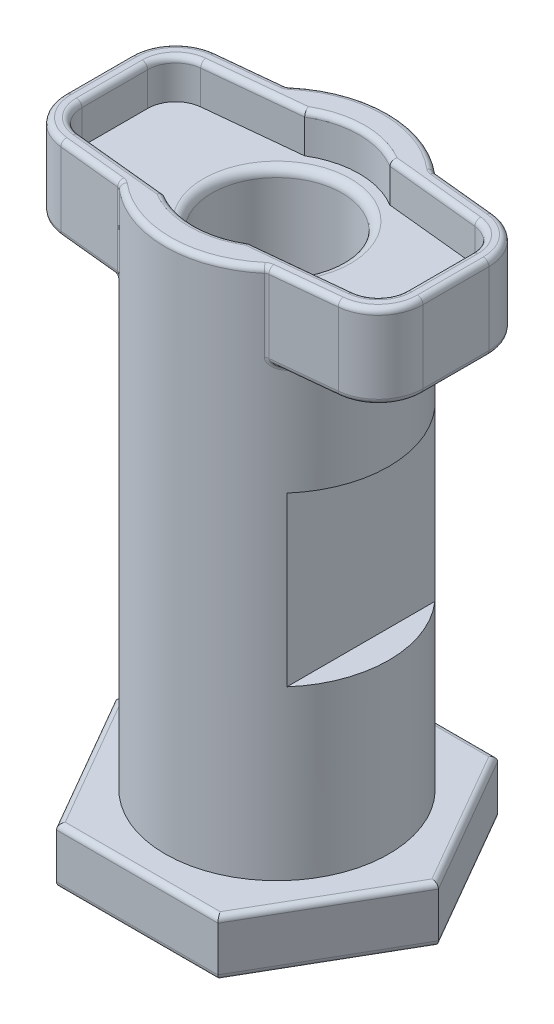
SolidWorks part; units mm, degrees
other "Markup1"
sketch "Sketch1" plane through (0, 0, 0) normal (0.5774, 0.5773, 0.5774) x (0.7071, 0, -0.7071)
sketch "Sketch2" plane through (0, 0, 0) normal (0.5774, 0.5773, 0.5774) x (0.7071, 0, -0.7071)
ref_plane "Front (z)" through (0, 0, 0) normal (0, 0, 1) x (1, 0, 0)
ref_plane "Top (y)" through (0, 0, 0) normal (0, 1, 0) x (1, 0, 0)
ref_plane "Right (x)" through (0, 0, 0) normal (1, 0, 0) x (0, 0, -1)
sketch "Sketch3" plane through (0, 0, 0) normal (0, 1, 0) x (1, 0, 0)
  line L1 (14.4338, 0) -> (7.2169, 12.5)
  line L2 (7.2169, 12.5) -> (-7.2169, 12.5)
  line L3 (-7.2169, 12.5) -> (-14.4338, 0)
  line L4 (-14.4338, 0) -> (-7.2169, -12.5)
  line L5 (-7.2169, -12.5) -> (7.2169, -12.5)
  line L6 (7.2169, -12.5) -> (14.4338, 0)
  circle A0 centre (0, 0) radius 12.5 construction
  dimension "D1" = 25
extrude "Boss-Extrude1" add sketch "Sketch3" along normal blind 5
sketch "Sketch4" plane through (0, 5, 0) normal (0, 1, 0) x (1, 0, 0)
  circle A0 centre (0, 0) radius 10
  dimension "D1" = 20
extrude "Boss-Extrude2" add sketch "Sketch4" along normal blind 40
sketch "Sketch5" plane through (0, 45, 0) normal (0, 1, 0) x (1, 0, 0)
  circle A0 centre (0, 0) radius 5.825
  dimension "D1" = 11.65
extrude "Cut-Extrude1" cut sketch "Sketch5" against normal through all
sketch "Sketch6" plane through (0, 45, 0) normal (0, 1, 0) x (1, 0, 0)
  line L0 (3.7022, 5.7942) -> (12.2018, 4.9323) construction
  line L1 (14, 2.9425) -> (14, -2.9425) construction
  line L2 (12.2018, -4.9323) -> (3.7022, -5.7942) construction
  line L3 (-3.7022, -5.7942) -> (-12.2018, -4.9323) construction
  line L4 (-14, -2.9425) -> (-14, 2.9425) construction
  line L5 (-12.2018, 4.9323) -> (-3.7022, 5.7942) construction
  line L6 (3.8093, 6.2859) -> (12.2522, 5.4298)
  line L7 (14.5, 2.9425) -> (14.5, -2.9425)
  line L8 (12.2522, -5.4298) -> (3.8093, -6.2859)
  line L9 (-3.8093, -6.2859) -> (-12.2522, -5.4298)
  line L10 (-14.5, -2.9425) -> (-14.5, 2.9425)
  line L11 (-12.2522, 5.4298) -> (-3.8093, 6.2859)
  line L12 (12.4035, -6.9221) -> (6.6027, -7.5103)
  line L13 (-6.6027, -7.5103) -> (-12.4035, -6.9221)
  line L14 (-16, -2.9425) -> (-16, 2.9425)
  line L15 (-12.4035, 6.9221) -> (-6.6027, 7.5103)
  line L16 (6.6027, 7.5103) -> (12.4035, 6.9221)
  line L17 (16, 2.9425) -> (16, -2.9425)
  line L19 (12.4035, -6.9221) -> (4.2809, -7.7457) construction
  line L20 (-4.2809, -7.7457) -> (-12.4035, -6.9221) construction
  line L21 (4.2809, 7.7457) -> (12.4035, 6.9221) construction
  line L22 (-12.4035, 6.9221) -> (-4.2809, 7.7457) construction
  arc A0 (-3.5962, -5.8301) -> (-3.7022, -5.7942) centre (-3.7274, -6.0429) ccw construction
  arc A1 (3.7022, -5.7942) -> (3.5962, -5.8301) centre (3.7274, -6.0429) ccw construction
  arc A2 (3.5962, 5.8301) -> (3.7022, 5.7942) centre (3.7274, 6.0429) ccw construction
  arc A3 (-3.7022, 5.7942) -> (-3.5962, 5.8301) centre (-3.7274, 6.0429) ccw construction
  arc A4 (3.5962, 5.8301) -> (-3.5962, 5.8301) centre (0, 0) ccw construction
  arc A5 (14, 2.9425) -> (12.2018, 4.9323) centre (12, 2.9425) ccw construction
  arc A6 (12.2018, -4.9323) -> (14, -2.9425) centre (12, -2.9425) ccw construction
  arc A7 (-3.5962, -5.8301) -> (3.5962, -5.8301) centre (0, 0) ccw construction
  arc A8 (-14, -2.9425) -> (-12.2018, -4.9323) centre (-12, -2.9425) ccw construction
  arc A9 (-12.2018, 4.9323) -> (-14, 2.9425) centre (-12, 2.9425) ccw construction
  arc A10 (14.5, 2.9425) -> (12.2522, 5.4298) centre (12, 2.9425) ccw
  arc A11 (12.2522, -5.4298) -> (14.5, -2.9425) centre (12, -2.9425) ccw
  arc A12 (3.8093, -6.2859) -> (3.8093, -6.2859) centre (3.8093, -6.2859) ccw
  arc A13 (-3.8093, -6.2859) -> (3.8093, -6.2859) centre (0, 0) ccw
  arc A14 (-3.8093, -6.2859) -> (-3.8093, -6.2859) centre (-3.8093, -6.2859) ccw
  arc A15 (-14.5, -2.9425) -> (-12.2522, -5.4298) centre (-12, -2.9425) ccw
  arc A16 (-12.2522, 5.4298) -> (-14.5, 2.9425) centre (-12, 2.9425) ccw
  arc A17 (-3.8093, 6.2859) -> (-3.8093, 6.2859) centre (-3.8093, 6.2859) ccw
  arc A18 (3.8093, 6.2859) -> (-3.8093, 6.2859) centre (0, 0) ccw
  arc A19 (3.8093, 6.2859) -> (3.8093, 6.2859) centre (3.8093, 6.2859) ccw
  arc A25 (-16, -2.9425) -> (-12.4035, -6.9221) centre (-12, -2.9425) ccw
  arc A26 (-12.4035, 6.9221) -> (-16, 2.9425) centre (-12, 2.9425) ccw
  arc A30 (16, 2.9425) -> (12.4035, 6.9221) centre (12, 2.9425) ccw
  arc A31 (12.4035, -6.9221) -> (16, -2.9425) centre (12, -2.9425) ccw
  arc A34 (-4.2809, -7.7457) -> (4.2809, -7.7457) centre (0, 0) ccw construction
  arc A35 (-4.2809, -7.7457) -> (-4.2809, -7.7457) centre (-4.2809, -7.7457) ccw construction
  arc A36 (4.2809, -7.7457) -> (4.2809, -7.7457) centre (4.2809, -7.7457) ccw construction
  arc A37 (-6.6027, -7.5103) -> (6.6027, -7.5103) centre (0, 0) ccw
  arc A40 (6.6027, 7.5103) -> (-6.6027, 7.5103) centre (0, 0) ccw
  arc A41 (4.2809, 7.7457) -> (-4.2809, 7.7457) centre (0, 0) ccw construction
  circle A42 centre (0, 0) radius 10 construction
  arc A43 (-4.2809, 7.7457) -> (-4.2809, 7.7457) centre (-4.2809, 7.7457) ccw construction
  arc A44 (4.2809, 7.7457) -> (4.2809, 7.7457) centre (4.2809, 7.7457) ccw construction
  dimension "D3" = 10
  dimension "D1" = 0.5
  dimension "D2" = 1.5
extrude "Boss-Extrude3" add sketch "Sketch6" along normal blind 7.5
sketch "Sketch7" plane through (0, 45, 0) normal (0, 1, 0) x (1, 0, 0)
  line L0 (12.2522, 5.4298) -> (3.8093, 6.2859) construction
  line L1 (14.5, -2.9425) -> (14.5, 2.9425) construction
  line L4 (-12.2522, -5.4298) -> (-3.8093, -6.2859) construction
  line L5 (-14.5, 2.9425) -> (-14.5, -2.9425) construction
  line L6 (-3.8093, 6.2859) -> (-12.2522, 5.4298) construction
  line L7 (12.2522, 5.4298) -> (3.8093, 6.2859)
  line L8 (14.5, -2.9425) -> (14.5, 2.9425)
  line L11 (-12.2522, -5.4298) -> (-3.8093, -6.2859)
  line L12 (-14.5, 2.9425) -> (-14.5, -2.9425)
  line L13 (-3.8093, 6.2859) -> (-12.2522, 5.4298)
  line L14 (3.8093, -6.2859) -> (12.2522, -5.4298)
  arc A1 (14.5, 2.9425) -> (12.2522, 5.4298) centre (12, 2.9425) ccw construction
  arc A2 (12.2522, -5.4298) -> (14.5, -2.9425) centre (12, -2.9425) ccw construction
  arc A4 (-14.5, -2.9425) -> (-12.2522, -5.4298) centre (-12, -2.9425) ccw construction
  arc A5 (-12.2522, 5.4298) -> (-14.5, 2.9425) centre (-12, 2.9425) ccw construction
  arc A6 (-3.8093, -6.2859) -> (3.8093, -6.2859) centre (0, 0) ccw
  arc A7 (14.5, 2.9425) -> (12.2522, 5.4298) centre (12, 2.9425) ccw
  arc A8 (12.2522, -5.4298) -> (14.5, -2.9425) centre (12, -2.9425) ccw
  arc A9 (3.8093, 6.2859) -> (-3.8093, 6.2859) centre (0, 0) ccw
  arc A10 (-14.5, -2.9425) -> (-12.2522, -5.4298) centre (-12, -2.9425) ccw
  arc A11 (-12.2522, 5.4298) -> (-14.5, 2.9425) centre (-12, 2.9425) ccw
  circle A14 centre (0, 0) radius 5.825 construction
  circle A15 centre (0, 0) radius 5.825
extrude "Boss-Extrude4" add sketch "Sketch7" along normal blind 4
fillet "Fillet2" radius 0.75 1 edges at (0, 49, 5.825)
fillet "Fillet3" radius 0.5 53 edges at (-16, 52.5, 0) (-14.9677, 52.5, -5.6245) (-14.9677, 52.5, 5.6245) (-9.5031, 52.5, -7.2162) (-9.5031, 52.5, 7.2162) (0, 52.5, -10) (0, 52.5, 10) (6.6027, 48.75, -7.5103) (6.6027, 48.75, 7.5103) (-6.6027, 48.75, 7.5103) (-6.6027, 48.75, -7.5103) (8.0307, 52.5, -5.8578) (13.8548, 52.5, -4.6188) (14.5, 52.5, 0) (13.8548, 52.5, 4.6188) (-8.0307, 52.5, -5.8578) (-13.8548, 52.5, -4.6188) (-14.5, 52.5, 0) (-13.8548, 52.5, 4.6188) (9.5031, 52.5, 7.2162) (14.9677, 52.5, 5.6245) (16, 52.5, 0) (14.9677, 52.5, -5.6245) (0, 5, 12.5) (-10.8253, 5, 6.25) (-10.8253, 5, -6.25) (0, 5, -12.5) (10.8253, 5, -6.25) (10.8253, 5, 6.25) (14.9677, 45, 5.6245) (16, 45, 0) (14.9677, 45, -5.6245) (9.5031, 45, -7.2162) (10, 45, 0) (9.5031, 45, 7.2162) (-14.9677, 45, -5.6245) (-16, 45, 0) (-14.9677, 45, 5.6245) (-9.5031, 45, 7.2162) (-10, 45, 0) (-9.5031, 45, -7.2162) (10.8253, 0, -6.25) (0, 0, -12.5) (-10.8253, 0, -6.25) (-10.8253, 0, 6.25) (0, 0, 12.5) (10.8253, 0, 6.25) (0, 0, 5.825) (0, 52.5, -7.35) (8.0307, 52.5, 5.8578) (-8.0307, 52.5, 5.8578) (0, 52.5, 7.35) (9.5031, 52.5, -7.2162)
sketch "Sketch8" plane through (0, 0, 0) normal (0, 0, 1) x (1, 0, 0)
  line L0 (10, 5) -> (10, 44.5) construction
  line L1 (10, 20) -> (7.5, 20)
  line L2 (10, 20) -> (10, 35)
  line L3 (10, 35) -> (7.5, 35)
  line L4 (7.5, 20) -> (7.5, 35)
  line L5 (-10, 44.5) -> (-10, 5) construction
  line L6 (-10, 20) -> (-7.5, 20)
  line L7 (-10, 20) -> (-10, 35)
  line L8 (-10, 35) -> (-7.5, 35)
  line L9 (-7.5, 20) -> (-7.5, 35)
  dimension "D1" = 15
  dimension "D2" = 2.5
  dimension "D3" = 20
extrude "Cut-Extrude2" cut sketch "Sketch8" against normal through all both and the other way through all
